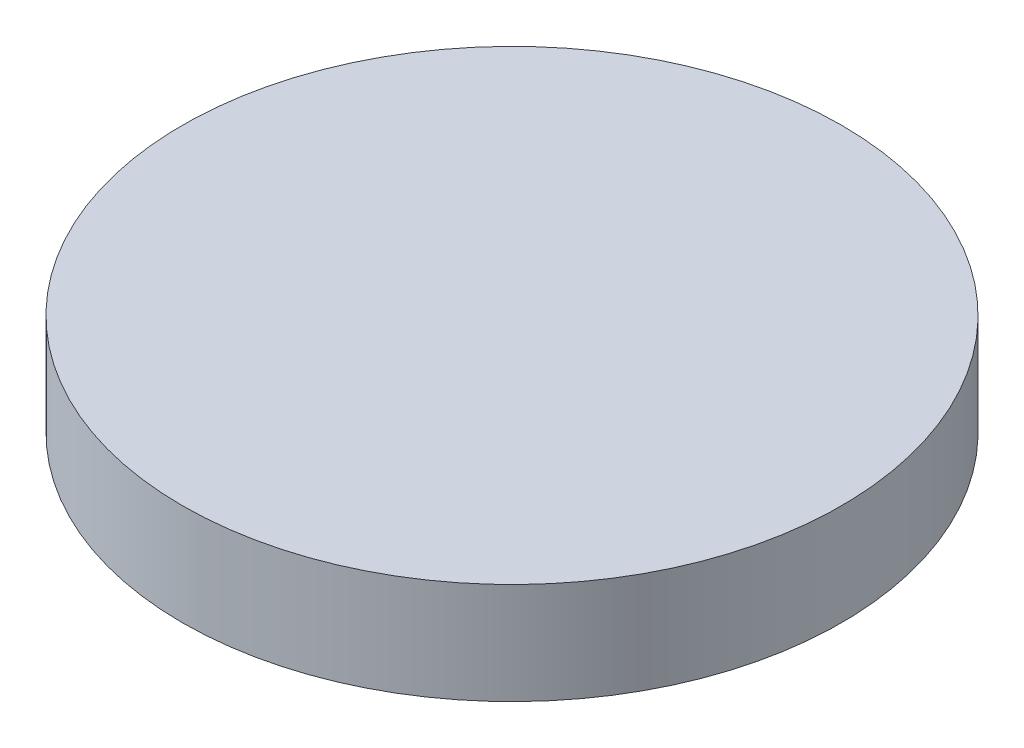
SolidWorks part; units mm, degrees
ref_plane "Alzado" through (0, 0, 0) normal (0, 0, 1) x (1, 0, 0)
ref_plane "Planta" through (0, 0, 0) normal (0, 1, 0) x (1, 0, 0)
ref_plane "Vista lateral" through (0, 0, 0) normal (1, 0, 0) x (0, 0, -1)
sketch "Croquis1" plane through (0, 0, 0) normal (0, 1, 0) x (1, 0, 0)
  circle A0 centre (0, 0) radius 13
  dimension "D1" = 26
extrude "Saliente-Extruir1" add sketch "Croquis1" along normal blind 4
sketch "Croquis3" plane through (0, 4, 0) normal (0, 1, 0) x (1, 0, 0)
  circle A0 centre (0, 0) radius 3.5 construction
  dimension "D1" = 7
sketch "Croquis6" plane through (0, 4, 0) normal (0, 1, 0) x (1, 0, 0)
  line L0 (0, 0) -> (0, 13) construction
  line L1 (0, 0.115) -> (0, -3.7) construction
  line L2 (-16.2152, 1.9838) -> (-1.9003, 3.0576)
  line L3 (-1.9003, 3.0576) -> (-1.9003, -3.0576) construction
  line L4 (-13.9629, -2.1527) -> (-1.9003, -3.0576)
  line L5 (-16.2152, 1.9838) -> (-15.4003, 2.045)
  line L6 (-13.9629, -2.1527) -> (-16.8535, -1.9359)
  line L7 (13.9629, -2.1527) -> (1.9003, -3.0576)
  line L8 (16.2152, 1.9838) -> (1.9003, 3.0576)
  line L9 (-16.2152, 1.9838) -> (-16.8535, -1.9359)
  line L10 (16.2152, 1.9838) -> (13.9629, -2.1527)
  arc A0 (-1.9003, -3.0576) -> (1.9003, -3.0576) centre (0, 0) ccw
  circle A1 centre (0, 0) radius 13 construction
  arc A2 (1.9003, 3.0576) -> (-1.9003, 3.0576) centre (0, 0) ccw
  point P10 (0, 3.6)
  point P14 (-7, 0)
  dimension "D4" = 3.6
  dimension "D1" = 85.71
  dimension "D2" = 85.71
  dimension "D3" = 4.71
